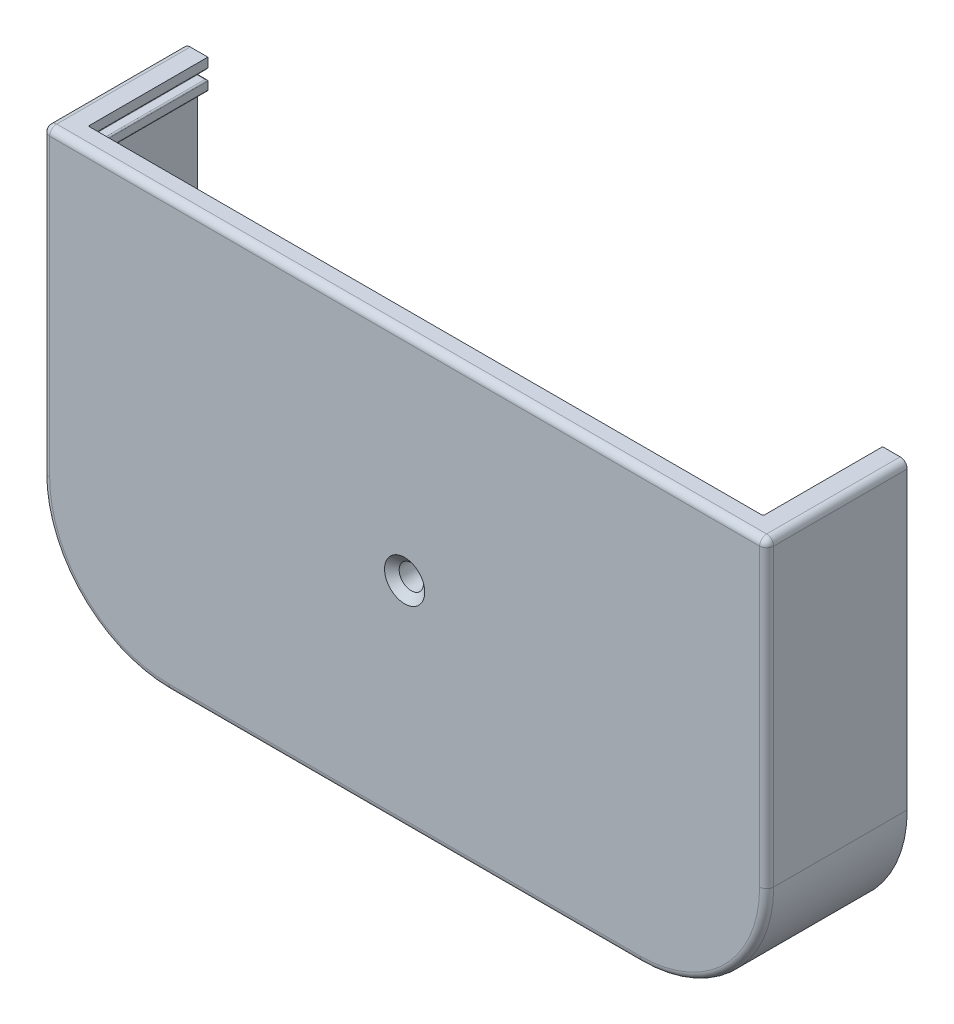
SolidWorks part; units mm, degrees
ref_plane "Plan de face" through (0, 0, 0) normal (0, 0, 1) x (1, 0, 0)
ref_plane "Plan de dessus" through (0, 0, 0) normal (0, 1, 0) x (1, 0, 0)
ref_plane "Plan de droite" through (0, 0, 0) normal (1, 0, 0) x (0, 0, -1)
sketch "Esquisse1" plane through (0, 0, 0) normal (0, 0, 1) x (1, 0, 0)
  line L1 (-33.5, -30.5) -> (33.5, -30.5)
  line L2 (-51.5, -12.5) -> (-51.5, 30.5)
  line L3 (-51.5, 30.5) -> (51.5, 30.5)
  line L4 (51.5, -12.5) -> (51.5, 30.5)
  line L5 (-51.5, -30.5) -> (51.5, 30.5) construction
  line L6 (-51.5, 30.5) -> (51.5, -30.5) construction
  arc A0 (33.5, -30.5) -> (51.5, -12.5) centre (33.5, -12.5) ccw
  arc A1 (-33.5, -30.5) -> (-51.5, -12.5) centre (-33.5, -12.5) cw
  point P0 (0, 0)
  dimension "D3" = 18
  dimension "D1" = 61
  dimension "D2" = 103
extrude "Boss.-Extru.1" add sketch "Esquisse1" along normal blind 20
sketch "Esquisse2" plane through (0, 0, 0) normal (0, 0, -1) x (-1, 0, 0)
  line L0 (-51.5, 30.5) -> (51.5, 30.5) construction
  line L1 (-49.5, 29) -> (-48, 29)
  line L2 (-49.5, 29) -> (-49.5, 27.75)
  line L3 (-49.5, 27.75) -> (49.5, 27.75)
  line L4 (49.5, 29) -> (49.5, 27.75)
  line L5 (48, 29) -> (49.5, 29)
  line L6 (-51.5, -12.5) -> (-51.5, 30.5) construction
  line L7 (-48, 29) -> (-48, 30.5)
  line L8 (-48, 30.5) -> (48, 30.5)
  line L9 (48, 29) -> (48, 30.5)
  line L10 (51.5, 30.5) -> (51.5, -12.5) construction
  point P4 (0, 28.5)
  point P12 (0, 30.5)
  dimension "D1" = 2
  dimension "D2" = 1.25
  dimension "D3" = 1.5
  dimension "D4" = 3.5
  dimension "D5" = 2
extrude "Enlèv. mat.-Extru.1" cut sketch "Esquisse2" against normal offset from surface (18 mm away) 2 up to face at (0, -5.4093, 20)
shell "Coque2" thickness 2 removed face at (0, 14.2889, 0)
sketch "Esquisse14" plane through (0, 0, 18) normal (0, 0, -1) x (-1, 0, 0)
  line L1 (-48, 30.5) -> (48, 30.5)
  line L2 (-48, 30.5) -> (-48, 29)
  line L3 (-48, 29) -> (48, 29)
  line L4 (48, 30.5) -> (48, 29)
extrude "Boss.-Extru.8" add sketch "Esquisse14" along normal blind 1
sketch "Esquisse3" plane through (0, 0, 0) normal (0, 0, -1) x (-1, 0, 0)
  line L0 (-48, 30.5) -> (-48, 29) construction
  line L1 (48, 29) -> (48, 30.5) construction
  line L2 (49.5, 25.75) -> (-49.5, 25.75) construction
  line L3 (-48, 27.75) -> (48, 27.75)
  line L4 (-48, 27.75) -> (-48, 25.75)
  line L5 (-48, 25.75) -> (48, 25.75)
  line L6 (48, 27.75) -> (48, 25.75)
  line L7 (49.5, 27.75) -> (-49.5, 27.75) construction
extrude "Enlèv. mat.-Extru.2" cut sketch "Esquisse3" against normal up to surface (17 mm away) up to face at (0, 29.75, 17)
sketch "Esquisse4" plane through (0, 0, 18) normal (0, 0, -1) x (-1, 0, 0)
  line L0 (0, 30.5) -> (0, -30.5) construction
  line L1 (-48, 30.5) -> (48, 30.5) construction
  line L2 (33.5, -30.5) -> (-33.5, -30.5) construction
  circle A0 centre (0, 0) radius 2.794
  dimension "D1" = 5.588
extrude "Boss.-Extru.2" add sketch "Esquisse4" along normal up to surface (18 mm away) up to face at (0, 11.2465, 0)
sketch "Esquisse5" plane through (0, 0, 0) normal (0, 0, -1) x (-1, 0, 0)
  circle A0 centre (0, 0) radius 1
  dimension "D1" = 2
extrude "Enlèv. mat.-Extru.3" cut sketch "Esquisse5" against normal blind 5
sketch "Esquisse7" plane through (0, 0, 18) normal (0, 0, -1) x (-1, 0, 0)
  line L0 (0, 10.92) -> (0, -16.55) construction
  line L1 (35, -28.4295) -> (49.375, -14.4961)
  line L2 (-35, -28.4295) -> (-49.375, -14.4961)
  arc A1 (35, -28.4295) -> (49.375, -14.4961) centre (33.5, -12.5) ccw
  arc A2 (33.5, -28.5) -> (49.5, -12.5) centre (33.5, -12.5) ccw construction
  arc A3 (33.5, -28.5) -> (49.5, -12.5) centre (33.5, -12.5) ccw construction
  arc A4 (-35, -28.4295) -> (-49.375, -14.4961) centre (-33.5, -12.5) cw
  dimension "D1" = 35
  dimension "D2" = 14.375
extrude "Boss.-Extru.4" add sketch "Esquisse7" along normal up to surface (18 mm away) up to face at (0, 11.2465, 0)
sketch "Esquisse8" plane through (0, 0, 0) normal (0, 0, -1) x (-1, 0, 0)
  line L0 (33.5, -30.5) -> (-33.5, -30.5) construction
  line L1 (-51.5, -12.5) -> (-51.5, 30.5) construction
  line L2 (0, 0) -> (0, -22.552) construction
  circle A0 centre (-44, -23) radius 1
  circle A1 centre (44, -23) radius 1
  dimension "D3" = 2
  dimension "D1" = 7.5
  dimension "D2" = 7.5
extrude "Boss.-Extru.5" add sketch "Esquisse8" along normal blind 3
fillet "Congé5" radius 0.5 4 edges at (-43, -23, 0) (43, -23, 0) (-43, -23, -3) (43, -23, -3)
fillet "Congé6" radius 1 8 edges at (-51.5, 9, 20) (-46.2279, -25.2279, 20) (0, -30.5, 20) (46.2279, -25.2279, 20) (0, 30.5, 20) (-51.5, 30.5, 10) (51.5, 9, 20) (51.5, 30.5, 10)
sketch "Esquisse9" plane through (0, 0, 0) normal (0, 0, -1) x (-1, 0, 0)
  line L0 (49.5, 25.75) -> (49.5, -12.5) construction
  line L1 (-49.5, 25.75) -> (49.5, 25.75)
  line L2 (-49.5, 25.75) -> (-49.5, 26.25)
  line L3 (-49.5, 26.25) -> (49.5, 26.25)
  line L4 (49.5, 25.75) -> (49.5, 26.25)
  dimension "D1" = 0.5
extrude "Enlèv. mat.-Extru.4" cut sketch "Esquisse9" against normal up to surface (18 mm away) up to face at (0, 28.375, 18)
fillet "Congé8" radius 0.2 43 edges at (-48, 27.75, 8.5) (-48.75, 29, 0) (-48.75, 27.75, 0) (48.75, 27.75, 0) (48.75, 29, 0) (-48, 29, 8.5) (0, 27.75, 17) (-49.5, 29, 9) (-49.5, 28.375, 0) (-49.5, 27.75, 9) (49.5, 27.75, 9) (49.5, 28.375, 0) (49.5, 29, 9) (0, 27.75, 18) (49.5, 28.375, 18) (0, 29, 18) (-49.5, 28.375, 18) (49.5, 6.875, 18) (0, 26.25, 18) (-49.5, 6.875, 18) (-49.4687, -13.5, 18) (-42.1875, -21.4628, 18) (-34.2508, -28.4824, 18) (0, -28.5, 18) (34.2508, -28.4824, 18) (42.1875, -21.4628, 18) (49.4687, -13.5, 18) (-49.375, -14.4961, 9) (-35, -28.4295, 9) (49.375, -14.4961, 9) (35, -28.4295, 9) (-48, 29.75, 17) (-48, 27, 17) (-48, 26.25, 8.5) (-49.5, 26.25, 9) (48, 27, 17) (0, 26.25, 17) (48, 29.75, 17) (0, 29, 17) (48, 29, 8.5) (48, 27.75, 8.5) (48, 26.25, 8.5) (49.5, 26.25, 9)
hole_wizard "CSK for #4 Flat Head Machine Screw (100)1" positions "Esquisse16" profile "Esquisse15" countersink size "#4" standard "Ansi Inch" end condition through all
sketch "Esquisse16" plane through (0, 0, 20) normal (0, 0, 1) x (1, 0, 0)
  point P1 (0, 0)
sketch "Esquisse15" plane through (0, 0, 20) normal (1, 0, 0) x (0, -1, 0)
  line L0 (0, 0) -> (0, 23)
  line L1 (0, 23) -> (1.7272, 23)
  line L2 (1.7272, 23) -> (1.7272, 0.9484)
  line L3 (1.7272, 0.9484) -> (2.8575, 0)
  line L5 (2.8575, 0) -> (0, 0)
  line L6 (-1.7272, 0.9484) -> (-2.8575, 0) construction
  line L11 (0, -6.35) -> (0, 107.95) construction
  dimension "Diamètre du perçage jusqu'au prochain" = 3.4544
  dimension "Profondeur du perçage jusqu'au prochain" = 23
  dimension "Diamètre du fraisage entrant" = 5.715
  dimension "Angle du fraisage entrant" = 100
fillet "Congé9" radius 5 1 edges at (-2.794, 0, 18)
